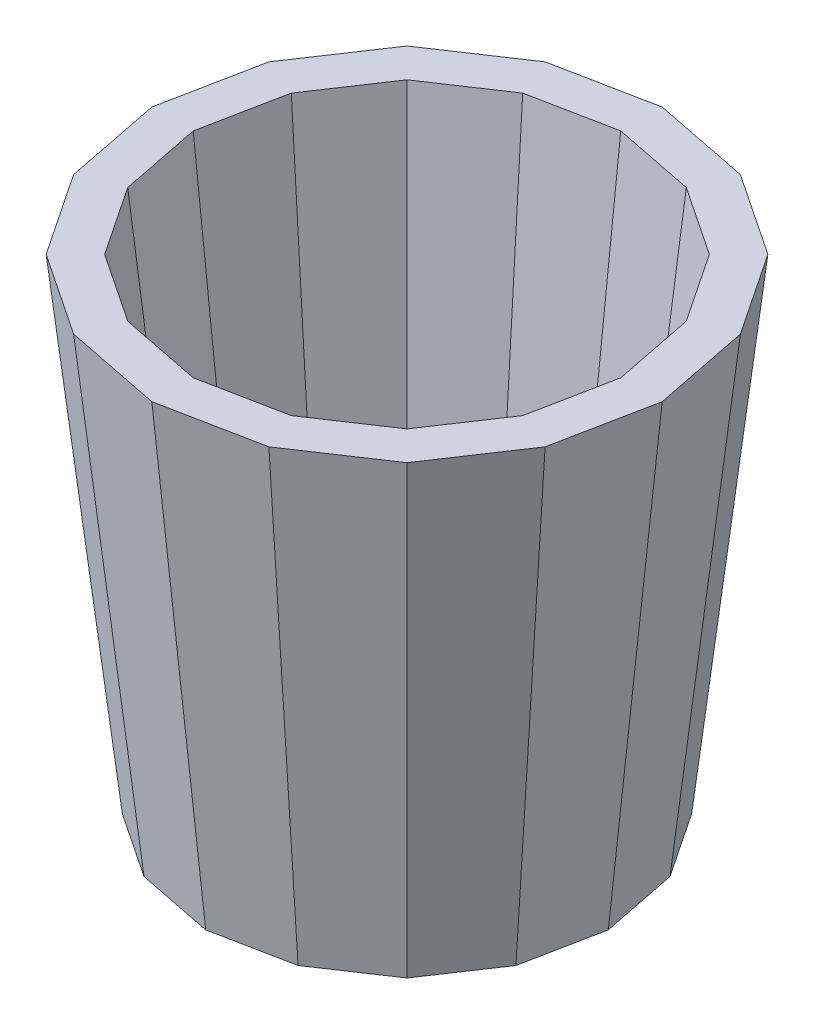
SolidWorks part; units mm, degrees
ref_plane "Front" through (0, 0, 0) normal (0, 0, 1) x (1, 0, 0)
ref_plane "Top" through (0, 0, 0) normal (0, 1, 0) x (1, 0, 0)
ref_plane "Right" through (0, 0, 0) normal (1, 0, 0) x (0, 0, -1)
sketch "Sketch1" plane through (0, 0, 0) normal (0, 1, 0) x (1, 0, 0)
  line L1 (120.4314, 0) -> (111.2641, 46.0871)
  line L2 (111.2641, 46.0871) -> (85.1579, 85.1579)
  line L3 (85.1579, 85.1579) -> (46.0871, 111.2641)
  line L4 (46.0871, 111.2641) -> (0, 120.4314)
  line L5 (0, 120.4314) -> (-46.0871, 111.2641)
  line L6 (-46.0871, 111.2641) -> (-85.1579, 85.1579)
  line L7 (-85.1579, 85.1579) -> (-111.2641, 46.0871)
  line L8 (-111.2641, 46.0871) -> (-120.4314, 0)
  line L9 (-120.4314, 0) -> (-111.2641, -46.0871)
  line L10 (-111.2641, -46.0871) -> (-85.1579, -85.1579)
  line L11 (-85.1579, -85.1579) -> (-46.0871, -111.2641)
  line L12 (-46.0871, -111.2641) -> (0, -120.4314)
  line L13 (0, -120.4314) -> (46.0871, -111.2641)
  line L14 (46.0871, -111.2641) -> (85.1579, -85.1579)
  line L15 (85.1579, -85.1579) -> (111.2641, -46.0871)
  line L16 (111.2641, -46.0871) -> (120.4314, 0)
  circle A0 centre (0, 0) radius 118.1173 construction
  dimension "D1" = 46.99
ref_plane "Plane1" through (0, -558.8, 0) normal (0, 1, 0) x (1, 0, 0)
sketch "Sketch2" plane through (0, -558.8, 0) normal (0, 1, 0) x (1, 0, 0)
  line L1 (58.2696, 0) -> (53.8341, 22.2988)
  line L2 (53.8341, 22.2988) -> (41.2029, 41.2029)
  line L3 (41.2029, 41.2029) -> (22.2988, 53.8341)
  line L4 (22.2988, 53.8341) -> (0, 58.2696)
  line L5 (0, 58.2696) -> (-22.2988, 53.8341)
  line L6 (-22.2988, 53.8341) -> (-41.2029, 41.2029)
  line L7 (-41.2029, 41.2029) -> (-53.8341, 22.2988)
  line L8 (-53.8341, 22.2988) -> (-58.2696, 0)
  line L9 (-58.2696, 0) -> (-53.8341, -22.2988)
  line L10 (-53.8341, -22.2988) -> (-41.2029, -41.2029)
  line L11 (-41.2029, -41.2029) -> (-22.2988, -53.8341)
  line L12 (-22.2988, -53.8341) -> (0, -58.2696)
  line L13 (0, -58.2696) -> (22.2988, -53.8341)
  line L14 (22.2988, -53.8341) -> (41.2029, -41.2029)
  line L15 (41.2029, -41.2029) -> (53.8341, -22.2988)
  line L16 (53.8341, -22.2988) -> (58.2696, 0)
  circle A0 centre (0, 0) radius 57.15 construction
  dimension "D1" = 114.3
loft "Loft1" add profiles "Sketch1", "Sketch2"
shell "Shell1" thickness 19.05 removed face at (0, -558.8, 0) removed face at (0, 0, 0)
ref_plane "Plane2" through (0, -228.6, 0) normal (0, 1, 0) x (1, 0, 0)
sketch "Sketch3" plane through (0, 0, 0) normal (0, 0, 1) x (1, 0, 0)
  line L0 (-85.1579, 0) -> (-111.2641, 0) construction
  line L1 (-73.6935, -152.4) -> (-35.5935, -152.4)
  line L2 (-73.6935, -152.4) -> (-73.6935, -228.6)
  line L3 (-73.6935, -228.6) -> (-35.5935, -228.6)
  line L5 (-35.5935, -152.4) -> (-35.5935, -228.6)
  dimension "D1" = 76.2
  dimension "D2" = 228.6
  dimension "D3" = 38.1
extrude "Boss-Extrude1" add sketch "Sketch3" against normal blind 35.56
sketch "Sketch4" plane through (0, -228.6, 0) normal (0, 1, 0) x (1, 0, 0)
  circle A0 centre (0, 0) radius 98.9543 construction
sketch "Sketch5" plane through (0, -558.8, 0) normal (0, 1, 0) x (1, 0, 0)
  circle A0 centre (0, 0) radius 16.7949 construction
ref_axis "Axis1" through (0, -558.8, 0) along (0, 1, 0)
pattern_circular "CirPattern1" count 16 over 360 about axis through (0, -558.8, 0) along (0, 1, 0) of "Boss-Extrude1"
sketch "Sketch6" plane through (0, 0, 0) normal (0, 0, 1) x (1, 0, 0)
  line L0 (-83.9397, -152.4) -> (-77.5502, -152.4) construction
  line L1 (98.9543, -228.6) -> (-98.9543, -228.6) construction
  line L3 (0, -222.0665) -> (0, -183.1987) construction
  line L4 (0, -228.6) -> (0, -152.4) construction
  line L5 (0, -228.6) -> (0, -152.4) construction
  line L6 (-81.1142, -152.4) -> (-14.7433, -152.4)
  line L7 (-14.7433, -152.4) -> (-14.7433, -228.6)
  line L8 (-36.3555, -228.6) -> (-14.7433, -228.6)
  line L9 (-46.0871, 0) -> (-22.2988, -558.8) construction
  spline S0 degree 3 poles (-81.1142, -152.4) (-79.6079, -169.7012) (-76.3866, -209.2895) (-64.3073, -217.6312) (-48.4491, -222.4766) (-35.4869, -222.6772) (-36.3555, -228.6) knots 0 0 0 0 0.382976 0.562428 0.835112 1 1 1 1
revolve "Cut-Revolve1" cut sketch "Sketch6" angle 360 about L3
sketch "Sketch8" plane through (0, -228.6, 0) normal (0, 1, 0) x (1, 0, 0)
  circle A0 centre (0, 0) radius 38.1
  dimension "D1" = 76.2
sketch "Sketch9" plane through (0, -228.6, 0) normal (0, 1, 0) x (1, 0, 0)
  circle A0 centre (0, 0) radius 146.5771
extrude "Cut-Extrude2" cut sketch "Sketch9" against normal through all
sketch "Sketch10" plane through (0, 0, 0) normal (0, 0, 1) x (1, 0, 0)
  line L0 (-46.679, -228.6) -> (-54.4757, -164.2866) construction
  line L1 (98.9543, -228.6) -> (-98.9543, -228.6) construction
  line L2 (-46.477, -228.6) -> (-46.477, -204.3825) construction
  line L3 (-54.9532, -219.9764) -> (-32.3931, -219.9764)
  line L4 (0, 0) -> (0, -228.6) construction
  line L5 (-32.3931, -219.9764) -> (-32.3931, -238.3091)
  line L6 (-32.3931, -238.3091) -> (-49.2649, -238.3091)
  spline S0 degree 3 poles (-54.9532, -219.9764) (-51.2563, -221.2087) (-43.7169, -222.9325) (-47.6722, -236.1239) (-49.2649, -238.3091) knots 0 0 0 0 0.374092 1 1 1 1
revolve "Cut-Revolve2" cut sketch "Sketch10" angle 360 about L4
